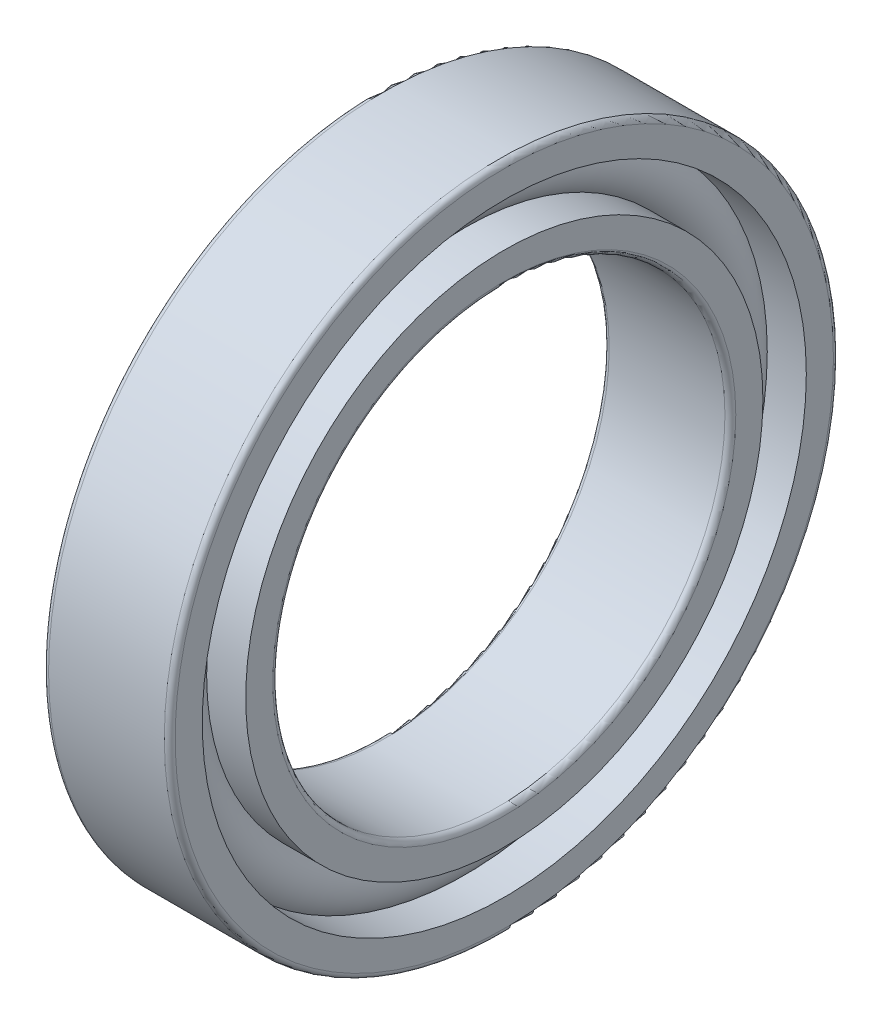
SolidWorks part; units mm, degrees
ref_plane "Plane1" through (0, 0, 0) normal (0, 0, 1) x (1, 0, 0)
ref_plane "Plane2" through (0, 0, 0) normal (0, 1, 0) x (1, 0, 0)
ref_plane "Plane3" through (0, 0, 0) normal (1, 0, 0) x (0, 0, -1)
sketch "Clipboard" plane through (0, 0, 0) normal (0, 0, 1) x (1, 0, 0)
  line L0 (-10, 0) -> (10, 0) construction
  line L1 (0, 0) -> (22.3471, -0.7804)
  line L2 (0, 0) -> (15.4906, 0.5409)
  line L3 (0, 0) -> (22.3471, -0.7804)
  line L4 (0, 0) -> (-22.3573, -0.3902)
  dimension "BallCLRad" = 15.5
  dimension "Count" = 2
  dimension "Show_count" = 2
  dimension "Max_count" = 2
  dimension "Min_count" = 1
sketch "CagSpiSke" plane through (0, 0, 0) normal (0, 0, 1) x (1, 0, 0)
  line L0 (0.18, 15.2) -> (0.18, 15.8)
  line L1 (0.18, 15.8) -> (-0.18, 15.8)
  line L2 (-0.18, 15.8) -> (-0.18, 15.2)
  line L3 (-0.18, 15.2) -> (0.18, 15.2)
  line L4 (-20.6375, 0) -> (20.6375, 0) construction
  line L5 (0, 0) -> (0, 23.7692) construction
  dimension "Thickness" = 0.36
  dimension "OD" = 31.6
  dimension "ID" = 30.4
revolve "CageSpine" add sketch "CagSpiSke" angle 0.001 about L4 reverse direction yes
ref_axis "Axis1" through (-50, 0, 0) along (1, 0, 0)
sketch "CagBalSke" plane through (0, 0, 0) normal (0, 0, 1) x (1, 0, 0)
  line L0 (-1.98, 15.5) -> (1.98, 15.5)
  line L1 (-1.905, 15.5) -> (1.905, 15.5) construction
  line L2 (-10, 0) -> (10, 0) construction
  line L3 (0, 0) -> (0, 24) construction
  arc A0 (1.98, 15.5) -> (-1.98, 15.5) centre (0, 15.5) cw
  dimension "CageWallOD" = 3.96
  dimension "BallCLRad" = 15.5
revolve "CageBall" [suppressed] add sketch "CagBalSke" angle 360 about L1 reverse direction yes
pattern_circular "CageBalls" [suppressed] count 2 every 180 about axis through (-50, 0, 0) along (1, 0, 0)
sketch "CagTrmODSke" plane through (0, 0, 0) normal (0, 0, 1) x (1, 0, 0)
  line L0 (1.981, 15.8) -> (1.981, 17.481)
  line L1 (1.981, 17.481) -> (-1.981, 17.481)
  line L2 (-1.981, 17.481) -> (-1.981, 15.8)
  line L3 (-1.981, 15.8) -> (1.981, 15.8)
  line L4 (-20.6375, 0) -> (20.6375, 0) construction
  line L5 (0, 0) -> (0, 25) construction
  dimension "Width" = 3.962
  dimension "ID" = 31.6
  dimension "OD" = 34.962
revolve "CageTrimOD" [suppressed] cut sketch "CagTrmODSke" angle 360 about L4 reverse direction yes
sketch "CagTrmIDSke" plane through (0, 0, 0) normal (0, 0, 1) x (1, 0, 0)
  line L0 (1.981, 13.521) -> (1.981, 15.2)
  line L1 (1.981, 15.2) -> (-1.981, 15.2)
  line L2 (-1.981, 15.2) -> (-1.981, 13.521)
  line L3 (-1.981, 13.521) -> (1.981, 13.521)
  line L4 (-20.6375, 0) -> (20.6375, 0) construction
  line L5 (0, 0) -> (0, 25) construction
  dimension "ID" = 27.042
  dimension "OD" = 30.4
  dimension "Width" = 3.962
revolve "CageTrimID" [suppressed] cut sketch "CagTrmIDSke" angle 360 about L4 reverse direction yes
sketch "BalSimSke" plane through (0, 0, 0) normal (0, 0, 1) x (1, 0, 0)
  line L0 (-10, 0) -> (10, 0) construction
  line L1 (-10, 15.5) -> (10, 15.5) construction
  line L2 (0, 0) -> (0, 23) construction
  circle A0 centre (0, 15.5) radius 1.8
  dimension "Ball_diameter" = 3.6
  dimension "BallCLRad" = 15.5
revolve "BallsSimplified" add sketch "BalSimSke" angle 360 about L0
sketch "BalDetSke" plane through (0, 0, 0) normal (0, 0, 1) x (1, 0, 0)
  line L0 (-1.8, 15.5) -> (1.8, 15.5)
  line L1 (-1.905, 15.5) -> (1.905, 15.5) construction
  line L2 (0, 0) -> (0, 25) construction
  arc A0 (1.8, 15.5) -> (-1.8, 15.5) centre (0, 15.5) cw
  dimension "Ball_diameter" = 3.6
  dimension "BallCLRad" = 15.5
revolve "BallDetailed" [suppressed] add sketch "BalDetSke" angle 360 about L1 reverse direction yes
sketch "InnRacSke" plane through (0, 0, 0) normal (0, 0, 1) x (1, 0, 0)
  line L0 (-1.3079, 14.3) -> (-3.5, 14.3)
  line L1 (-3.5, 14.3) -> (-3.5, 12.8)
  line L2 (-3.2, 12.5) -> (3.2, 12.5)
  line L3 (3.5, 12.8) -> (3.5, 14.3)
  line L4 (3.5, 14.3) -> (1.3079, 14.3)
  line L5 (-20.6375, 0) -> (20.6375, 0) construction
  line L6 (0, 0) -> (0, 30) construction
  arc A0 (-3.5, 12.8) -> (-3.2, 12.5) centre (-3.2, 12.8) ccw
  arc A1 (3.2, 12.5) -> (3.5, 12.8) centre (3.2, 12.8) ccw
  arc A2 (1.3079, 14.3) -> (-1.3079, 14.3) centre (0, 15.5) cw
  dimension "Fillet_radius" = 0.3
  dimension "Ball_diameter" = 3.55
  dimension "ID" = 25
  dimension "OD" = 28.6
  dimension "Width" = 7
  dimension "BallCLRad" = 15.5
revolve "InnerRace" add sketch "InnRacSke" angle 360 about L5 reverse direction yes
sketch "OutRacSke" plane through (0, 0, 0) normal (0, 0, 1) x (1, 0, 0)
  line L0 (-1.3079, 16.7) -> (-3.5, 16.7)
  line L1 (-3.5, 16.7) -> (-3.5, 18.2)
  line L2 (-3.2, 18.5) -> (3.2, 18.5)
  line L3 (3.5, 18.2) -> (3.5, 16.7)
  line L4 (3.5, 16.7) -> (1.3079, 16.7)
  line L5 (-20.6375, 0) -> (20.6375, 0) construction
  line L6 (0, 0) -> (0, 30) construction
  arc A0 (-3.5, 18.2) -> (-3.2, 18.5) centre (-3.2, 18.2) cw
  arc A1 (3.2, 18.5) -> (3.5, 18.2) centre (3.2, 18.2) cw
  arc A2 (1.3079, 16.7) -> (-1.3079, 16.7) centre (0, 15.5) ccw
  dimension "Fillet_radius" = 0.3
  dimension "Ball_diameter" = 3.55
  dimension "OD" = 37
  dimension "ID" = 33.4
  dimension "Width" = 7
  dimension "BallCLRad" = 15.5
revolve "OuterRace" add sketch "OutRacSke" angle 360 about L5 reverse direction yes
pattern_circular "BallsDetailed" [suppressed] count 2 every 180 about axis through (-50, 0, 0) along (1, 0, 0)
equation "\"BallCLRad@Clipboard\" = ( \"OD@OutRacSke\" + \"ID@InnRacSke\" ) / 4"
equation "\"BallCLRad@BalSimSke\" = \"BallCLRad@Clipboard\""
equation "\"BallCLRad@BalDetSke\" = \"BallCLRad@Clipboard\""
equation "\"BallCLRad@InnRacSke\" = \"BallCLRad@Clipboard\""
equation "\"BallCLRad@OutRacSke\" = \"BallCLRad@Clipboard\""
equation "\"Ball_diameter@InnRacSke\" = \"Ball_diameter@BalDetSke\" - 0.05"
equation "\"Ball_diameter@OutRacSke\" = \"Ball_diameter@BalDetSke\" - 0.05"
equation "\"Ball_diameter@BalSimSke\" = \"Ball_diameter@BalDetSke\""
equation "\"Width@OutRacSke\" = \"Width@InnRacSke\""
equation "\"Fillet_radius@OutRacSke\" = \"Fillet_radius@InnRacSke\""
equation "\"Max_count@Clipboard\" = int( 3.14159265 / atn(( \"Ball_diameter@BalDetSke\" / 2) / sqr( \"BallCLRad@Clipboard\"  *  \"BallCLRad@Clipboard\" - ( \"Ball_diameter@BalDetSke\" / 2) *  ( \"Ball_diameter@BalDetSke\" / 2))))"
equation "\"Max_count@Clipboard\" = ((sgn( \"Max_count@Clipboard\" - \"Count@Clipboard\" )-1)*( \"Max_count@Clipboard\" - \"Count@Clipboard\" ))/-2+ \"Count@Clipboard\""
equation "\"Count@BallsDetailed\" = int( \"Show_count@Clipboard\" ) "
equation "\"Count@BallsDetailed\" = ((sgn( \"Count@BallsDetailed\" - \"Max_count@Clipboard\" )-1)*( \"Count@BallsDetailed\" - \"Max_count@Clipboard\" ))/-2+ \"Max_count@Clipboard\""
equation "\"Count@BallsDetailed\" = ((sgn( \"Count@BallsDetailed\" - \"Min_count@Clipboard\" )+1)*( \"Count@BallsDetailed\" - \"Min_count@Clipboard\"))/2 +\"Min_count@Clipboard\""
equation "\"Angle@BallsDetailed\" = 360.0 / \"Max_count@Clipboard\""
equation "\"BallCLRad@CagBalSke\" = \"BallCLRad@Clipboard\""
equation "\"Count@CageBalls\" = \"Count@BallsDetailed\""
equation "\"Angle@CageBalls\" = \"Angle@BallsDetailed\""
equation "\"Angle@CageSpine\" =  \"Angle@CageBalls\" * ( \"Count@CageBalls\" -1 + int( \"Count@CageBalls\" / \"Max_count@Clipboard\" ) )  + 0.001 -  int( \"Count@CageBalls\" / \"Max_count@Clipboard\" ) * 0.001"
equation "\"Angle@CageSpine\" =  \"Angle@CageSpine\" * int( \"Min_count@Clipboard\" / 2) + int(1 / \"Min_count@Clipboard\")  * 0.001"
equation "\"CageWallOD@CagBalSke\" =  \"Ball_diameter@BalDetSke\" * 1.1"
equation "\"Thickness@CagSpiSke\" =  \"Ball_diameter@BalDetSke\" * 0.1"
equation "\"OD@CagTrmODSke\" = \"BallCLRad@Clipboard\" * 2 + \"CageWallOD@CagBalSke\" + 0.002"
equation "\"ID@CagTrmODSke\" = \"BallCLRad@Clipboard\" * 2 + \"Ball_diameter@BalDetSke\" / 6"
equation "\"OD@CagTrmIDSke\" = \"BallCLRad@Clipboard\" * 2 - \"Ball_diameter@BalDetSke\" / 6"
equation "\"ID@CagTrmIDSke\" = \"BallCLRad@Clipboard\" * 2 - \"CageWallOD@CagBalSke\" + 0.002"
equation "\"OD@CagSpiSke\" = \"ID@CagTrmODSke\""
equation "\"ID@CagSpiSke\" = \"OD@CagTrmIDSke\""
equation "\"Width@CagTrmODSke\" = \"CageWallOD@CagBalSke\" + 0.002"
equation "\"Width@CagTrmIDSke\" = \"CageWallOD@CagBalSke\" + 0.002"
